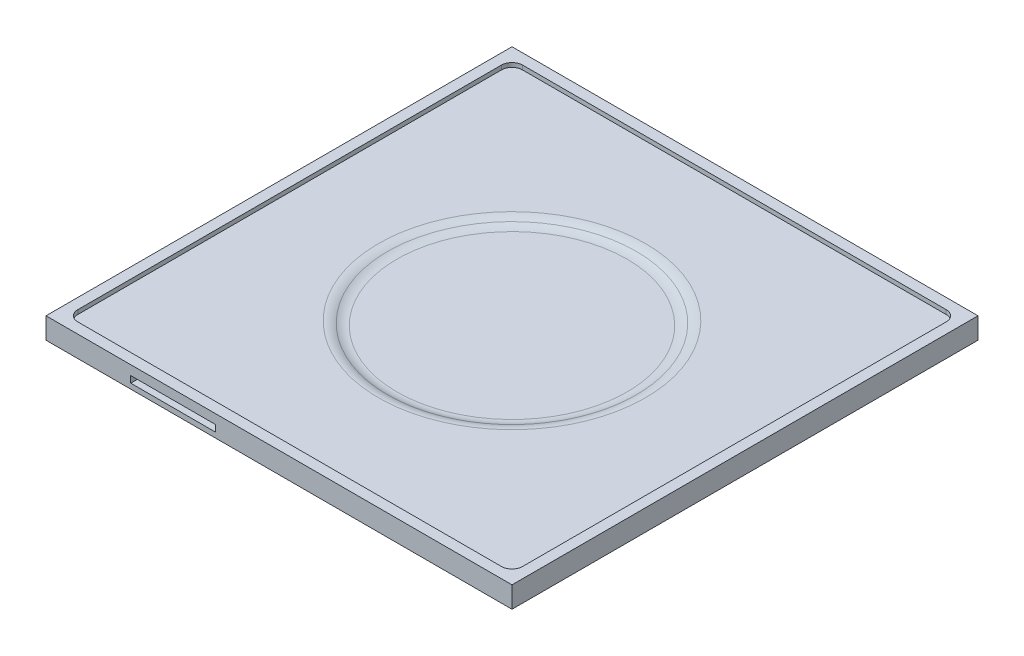
SolidWorks part; units mm, degrees
ref_plane "Front Plane" through (0, 0, 0) normal (0, 0, 1) x (1, 0, 0)
ref_plane "Top Plane" through (0, 0, 0) normal (0, 1, 0) x (1, 0, 0)
ref_plane "Right Plane" through (0, 0, 0) normal (1, 0, 0) x (0, 0, -1)
sketch "Sketch1" plane through (0, 0, 0) normal (0, 1, 0) x (1, 0, 0)
  line L1 (110, 110) -> (-110, 110)
  line L2 (110, 110) -> (110, -110)
  line L3 (110, -110) -> (-110, -110)
  line L4 (-110, 110) -> (-110, -110)
  line L5 (110, 110) -> (-110, -110) construction
  line L6 (110, -110) -> (-110, 110) construction
  point P0 (0, 0)
extrude "Boss-Extrude1" add sketch "Sketch1" along normal blind 10
sketch "Sketch2" plane through (0, 10, 0) normal (0, 1, 0) x (1, 0, 0)
  line L1 (105, 105) -> (-105, 105)
  line L2 (105, 105) -> (105, -105)
  line L3 (105, -105) -> (-105, -105)
  line L4 (-105, 105) -> (-105, -105)
  line L5 (105, 105) -> (-105, -105) construction
  line L6 (105, -105) -> (-105, 105) construction
  point P0 (0, 0)
extrude "Cut-Extrude1" cut sketch "Sketch2" against normal blind 2
sketch "Sketch3" plane through (0, 8, 0) normal (0, 1, 0) x (1, 0, 0)
  circle A0 centre (0, 0) radius 60.325
extrude "Cut-Extrude2" cut sketch "Sketch3" against normal blind 2
fillet "Fillet1" radius 10 1 edges at (0, 6, 60.325)
fillet "Fillet2" radius 10 1 edges at (0, 8, 60.325)
fillet "Fillet3" radius 5 1 edges at (-105, 9, -105)
fillet "Fillet4" radius 5 1 edges at (105, 9, -105)
fillet "Fillet5" radius 5 1 edges at (-105, 9, 105)
fillet "Fillet6" radius 5 1 edges at (105, 9, 105)
sketch "Sketch4" plane through (0, 0, 110) normal (0, 0, 1) x (1, 0, 0)
  line L1 (-70, 5.55) -> (-30, 5.55)
  line L2 (-70, 5.55) -> (-70, 2.45)
  line L3 (-70, 2.45) -> (-30, 2.45)
  line L4 (-30, 5.55) -> (-30, 2.45)
extrude "Cut-Extrude3" cut sketch "Sketch4" against normal blind 20
